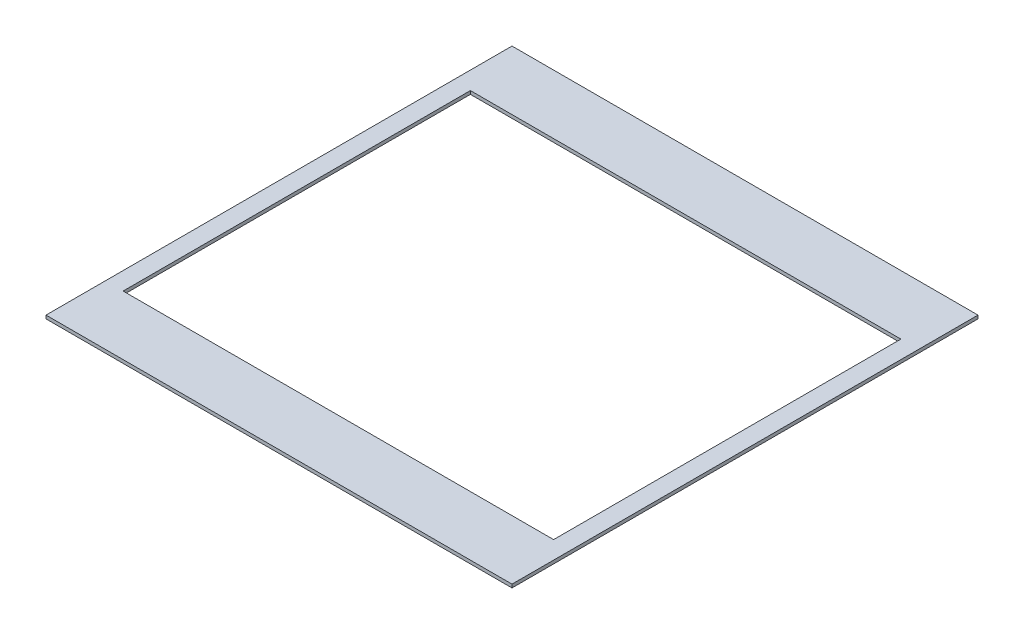
SolidWorks part; units mm, degrees
ref_plane "Front Plane" through (0, 0, 0) normal (0, 0, 1) x (1, 0, 0)
ref_plane "Top Plane" through (0, 0, 0) normal (0, 1, 0) x (1, 0, 0)
ref_plane "Right Plane" through (0, 0, 0) normal (1, 0, 0) x (0, 0, -1)
sketch "Sketch1" plane through (0, 0, 0) normal (0, 1, 0) x (1, 0, 0)
  line L1 (-210, -210) -> (210, -210)
  line L2 (-210, -210) -> (-210, 210)
  line L3 (-210, 210) -> (210, 210)
  line L4 (210, -210) -> (210, 210)
  line L5 (-210, -210) -> (210, 210) construction
  line L6 (-210, 210) -> (210, -210) construction
  line L7 (-194, 156.5) -> (194, 156.5)
  line L8 (-194, 156.5) -> (-194, -156.5)
  line L9 (-194, -156.5) -> (194, -156.5)
  line L10 (194, 156.5) -> (194, -156.5)
  line L11 (-194, 156.5) -> (194, -156.5) construction
  line L12 (-194, -156.5) -> (194, 156.5) construction
  point P0 (0, 0)
  point P5 (0, 0)
  dimension "D1" = 420
  dimension "D2" = 420
  dimension "D3" = 313
  dimension "D4" = 388
extrude "Boss-Extrude1" add sketch "Sketch1" along normal blind 3
